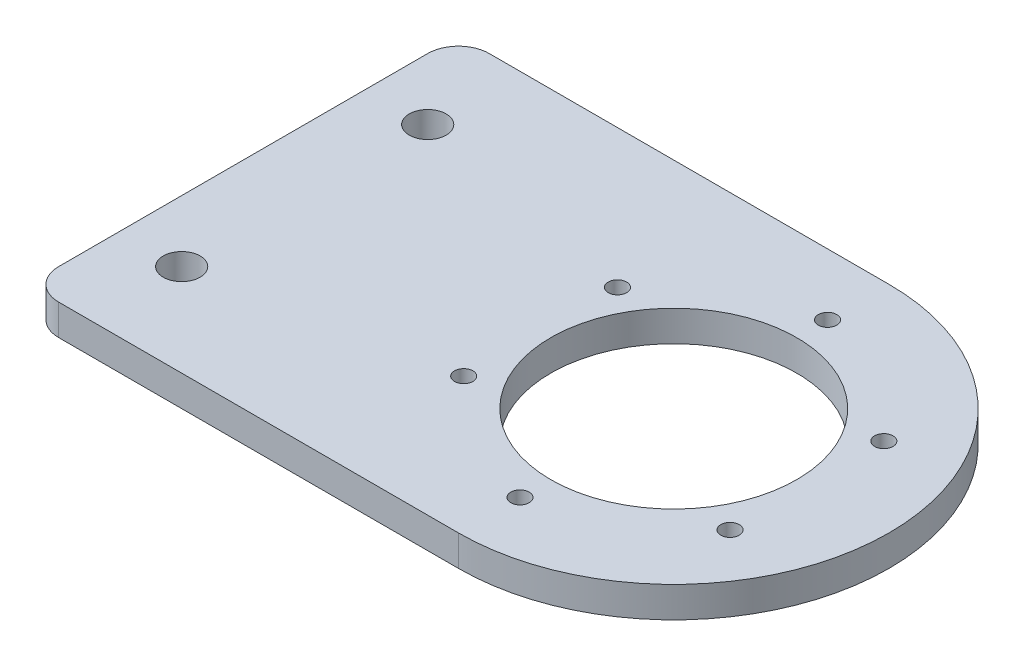
SolidWorks part; units mm, degrees
ref_plane "Front Plane" through (0, 0, 0) normal (0, 0, 1) x (1, 0, 0)
ref_plane "Top Plane" through (0, 0, 0) normal (0, 1, 0) x (1, 0, 0)
ref_plane "Right Plane" through (0, 0, 0) normal (1, 0, 0) x (0, 0, -1)
sketch "Sketch1" plane through (0, 0, 0) normal (0, 1, 0) x (1, 0, 0)
  line L0 (-70, 35) -> (0, 35)
  line L1 (0, -35) -> (-70, -35)
  line L2 (-70, -35) -> (-70, 35)
  line L3 (-60, 20) -> (-60, -20) construction
  line L4 (-103.0809, 0) -> (63.3859, 0) construction
  circle A0 centre (0, 0) radius 25 construction
  circle A1 centre (0, 25) radius 1.5
  arc A2 (0, 35) -> (0, -35) centre (0, 0) cw
  circle A3 centre (21.6506, 12.5) radius 1.5
  circle A4 centre (21.6506, -12.5) radius 1.5
  circle A5 centre (0, -25) radius 1.5
  circle A6 centre (-21.6506, -12.5) radius 1.5
  circle A7 centre (-21.6506, 12.5) radius 1.5
  circle A8 centre (0, 0) radius 20
  circle A9 centre (-60, 20) radius 3
  circle A10 centre (-60, -20) radius 3
  point P23 (0, 0)
  point P28 (-60, 0)
  dimension "D1" = 3
  dimension "D2" = 50
  dimension "D6" = 40
  dimension "D8" = 6
  dimension "D3" = 70
  dimension "D4" = 70
  dimension "D7" = 40
  dimension "D9" = 10
  dimension "D5" = 6
extrude "Boss-Extrude1" add sketch "Sketch1" along normal blind 5
fillet "Fillet1" radius 5 2 edges at (-70, 2.5, -35) (-70, 2.5, 35)
